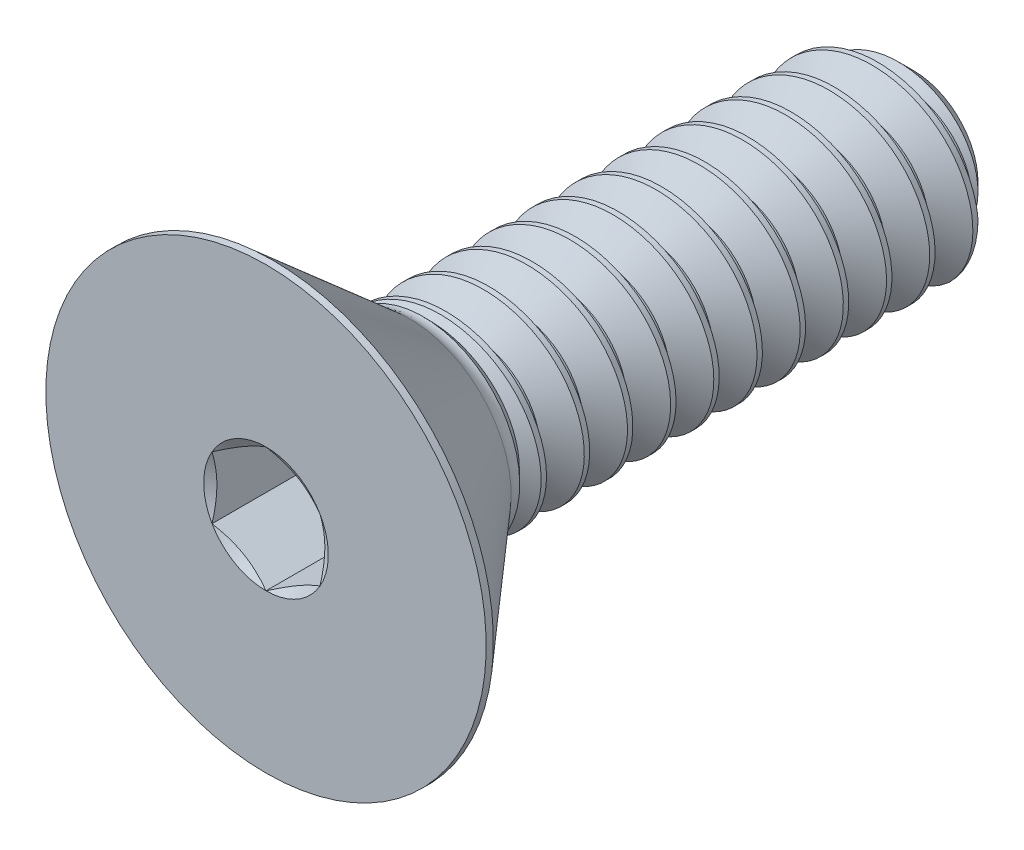
SolidWorks part; units mm, degrees
ref_plane "Front" through (0, 0, 0) normal (0, 0, 1) x (1, 0, 0)
ref_plane "Top" through (0, 0, 0) normal (0, 1, 0) x (1, 0, 0)
ref_plane "Right" through (0, 0, 0) normal (1, 0, 0) x (0, 0, -1)
sketch "Sketch1" plane through (0, 0, 0) normal (1, 0, 0) x (0, 0, -1)
  line L0 (0, 3.2385) -> (0.1054, 3.2385) construction
  line L1 (0.1054, 3.2385) -> (2.1082, 1.4975) construction
  line L2 (0, 1.4224) -> (9.525, 1.4224)
  line L3 (9.525, 1.4224) -> (9.525, 0)
  line L4 (9.525, 0) -> (0, 0)
  line L5 (0, 0) -> (0, 3.2385) construction
  line L6 (0, 3.2385) -> (0, -3.2385) construction
  line L7 (9.525, 1.4224) -> (9.525, -1.4224) construction
  line L8 (0, -3.2385) -> (0.1054, -3.2385) construction
  line L9 (0.1054, -3.2385) -> (2.1082, -1.4975) construction
  line L11 (0, 1.4224) -> (0, 0)
  line L12 (2.3091, 1.4224) -> (2.3091, 0) construction
  line L13 (-15.875, 0) -> (-15.875, 1.4224) construction
  arc A1 (2.1082, 1.4975) -> (2.3091, 1.4224) centre (2.3091, 1.7286) ccw construction
  dimension "D1" = 0.1054
  dimension "Min Thread" = 25.4
revolve "Revolve1" add sketch "Sketch1" angle 360 mid plane about L4
sketch "Sketch3" plane through (0, 0, -9.525) normal (0, 0, -1) x (-1, 0, 0)
  circle A0 centre (0, 0) radius 1.4224
curve "Helix/Spiral1" pitch 0.635 height 9.525 radius 1.4224 centre (0, 0, -9.525) axis (0, 0, 1) start towards (0, 1, 0)
sketch "Sketch2" plane through (0, 0, 0) normal (1, 0, 0) x (0, 0, -1)
  line L0 (9.525, 1.4224) -> (10.0806, 1.4224)
  line L1 (10.0806, 1.4224) -> (9.8425, 1.01)
  line L2 (9.8425, 1.01) -> (9.7631, 1.01)
  line L3 (9.7631, 1.01) -> (9.525, 1.4224)
  line L4 (9.6441, 1.2162) -> (9.9616, 1.2162) construction
  dimension "D1" = 60
  dimension "D2" = 0.0794
  dimension "D3" = 0.3175
ref_plane "Plane2" through (0, 0, 15.875) normal (0, 0, 1) x (1, 0, 0)
chamfer "Chamfer1" distance 0.4763 angle 45 1 edges at (0, 1.4224, -9.525)
sweep "Cut-Sweep1" cut profiles "Sketch2" path "Helix/Spiral1" align with end faces yes
sketch "Sketch7" plane through (0, 0, 0) normal (1, 0, 0) x (0, 0, -1)
  line L0 (0, 3.2385) -> (0.1054, 3.2385) construction
  line L1 (0.1054, 3.2385) -> (2.1082, 1.4975) construction
  line L2 (0, 3.2385) -> (0.1054, 3.2385)
  line L3 (0.1054, 3.2385) -> (2.1082, 1.4975)
  line L4 (2.3091, 1.4224) -> (2.3091, 0) construction
  line L5 (2.3091, 1.4224) -> (2.3091, 0)
  line L7 (0, 0) -> (0, 3.2385) construction
  line L8 (0, 0) -> (0, 3.2385)
  line L9 (0, 0) -> (2.3091, 0)
  line L10 (5.7417, 0) -> (-5.7417, 0) construction
  arc A0 (2.1082, 1.4975) -> (2.3091, 1.4224) centre (2.3091, 1.7286) ccw construction
  arc A1 (2.1082, 1.4975) -> (2.3091, 1.4224) centre (2.3091, 1.7286) ccw
revolve "Revolve2" add sketch "Sketch7" angle 360 mid plane about L9
ref_plane "Plane1" through (0, 0, -2.3091) normal (0, 0, 1) x (1, 0, 0)
sketch "Sketch8" plane through (0, 0, -2.3091) normal (0, 0, 1) x (1, 0, 0)
  circle A0 centre (0, 0) radius 1.4224
extrude "Boss-Extrude1" add sketch "Sketch8" against normal through all draft 46
sketch "Sketch5" plane through (0, 0, 0) normal (0, 0, 1) x (1, 0, 0)
  line L0 (0, 0) -> (-0.9165, 0) construction
  line L1 (0, 0) -> (-2.7496, 1.5875) construction
  line L2 (0, 0) -> (-2.7496, -1.5875) construction
  line L6 (0, 0.9165) -> (0, 0.7559) construction
  line L7 (0, 0.7559) -> (0, 0.5953) construction
  line L9 (0, 0.9165) -> (-0.7937, 0.4583)
  line L10 (-0.7937, 0.4583) -> (-0.7937, -0.4583)
  line L11 (-0.7937, -0.4583) -> (0, -0.9165)
  line L12 (0, -0.9165) -> (0.7937, -0.4583)
  line L13 (0.7937, -0.4583) -> (0.7938, 0.4583)
  line L14 (0.7938, 0.4583) -> (0, 0.9165)
  circle A0 centre (0, 0) radius 0.9165 construction
  circle A1 centre (0, 0) radius 0.7559 construction
  circle A2 centre (0, 0) radius 0.5953 construction
  circle A3 centre (0, 0) radius 0.7938 construction
  dimension "D3" = 1.1906
  dimension "D4" = 30
  dimension "D5" = 30
  dimension "Hex" = 1.5875
extrude "Cut-Extrude2" cut sketch "Sketch5" against normal blind 1.4757
sketch "Sketch6" plane through (0, 0, 0) normal (0, 0, 1) x (1, 0, 0)
  circle A0 centre (0, 0) radius 0.9165
extrude "Cut-Extrude3" cut sketch "Sketch6" against normal blind 1.4757 draft 60
sketch "Sketch9" [suppressed] plane through (0, 0, -3.6076) normal (0, 0, 1) x (1, 0, 0)
  circle A1 centre (0, 0) radius 2.413
  circle A2 centre (0, 0) radius 2.413
  point P0 (0, 2.413)
  dimension "D1" = 0
extrude "Boss-Extrude2" [suppressed] add sketch "Sketch9" against normal up to surface (15.4424 mm away) up to plane "Plane2"
sketch "Sketch10" plane through (0, 0, 0) normal (1, 0, 0) x (0, 0, -1)
  line L0 (9.525, 1.4224) -> (9.525, -1.4224) construction
  point P0 (8.5725, -1.4224)
  dimension "D1" = 0.9525
equation "\"D3@Helix/Spiral1\" = \"Lg@Sketch1\""
equation "\"D2@Sketch2\" = \"D4@Helix/Spiral1\" * .125"
equation "\"D3@Sketch2\" = \"D4@Helix/Spiral1\" * .5"
equation "\"D1@Chamfer1\" = \"D4@Helix/Spiral1\" * .75"
equation "\"D1@Cut-Extrude2\" = \"Head Ht@Sketch1\" * .7"
equation "\"D1@Sketch1\" = \"Head Ht@Sketch1\" * .05"
equation "\"D1@Sketch10\" = \"D4@Helix/Spiral1\" * 1.5"
equation "\"D1@Cut-Extrude3\" = \"D1@Cut-Extrude2\""
equation "\"D3@Sketch5\" = \"Hex@Sketch5\" * .75"
